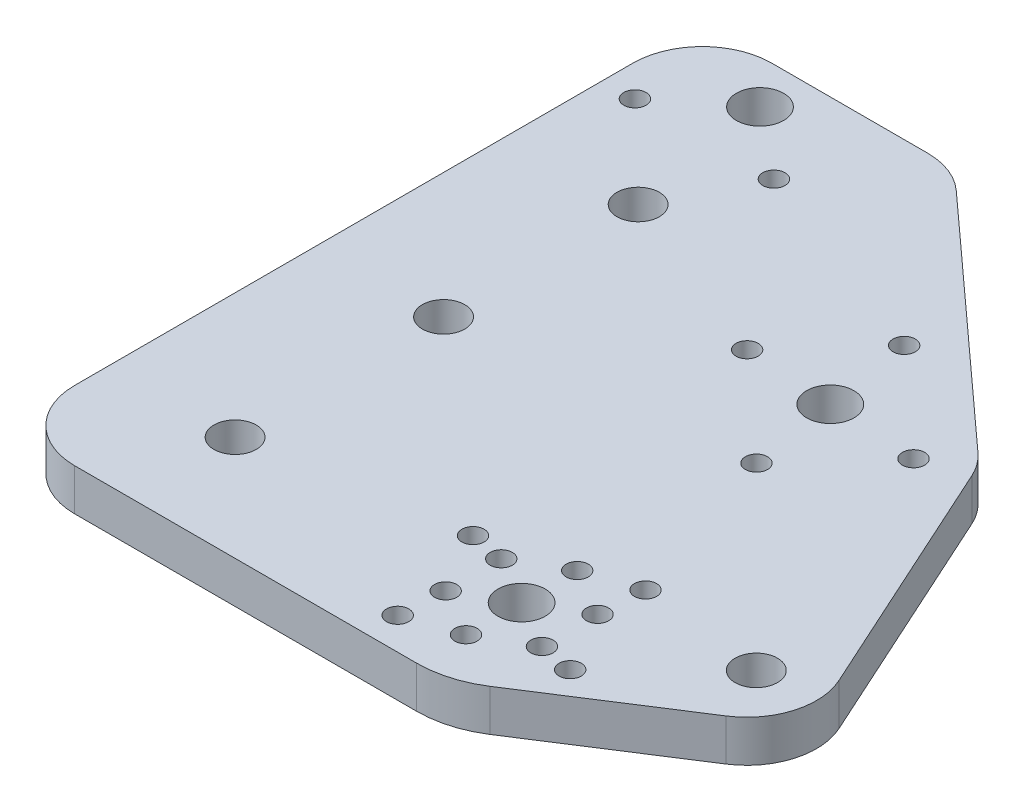
SolidWorks part; units mm, degrees
material "Policarbonato"
ref_plane "Plano frontal" through (0, 0, 0) normal (0, 0, 1) x (1, 0, 0)
ref_plane "Plano superior" through (0, 0, 0) normal (0, 1, 0) x (1, 0, 0)
ref_plane "Plano direito" through (0, 0, 0) normal (1, 0, 0) x (0, 0, -1)
ref_plane "Plano1" through (0, -6, 0) normal (0, -1, 0) x (1, 0, 0)
sketch "Esboço1" plane through (0, -6, 0) normal (0, -1, 0) x (1, 0, 0)
  line L0 (151.2357, -14.2909) -> (167.1948, 20.7865)
  line L1 (163.5005, 33.3393) -> (142.8288, 46.6294)
  line L2 (134.6661, 49.0269) -> (75.4374, 49.0269)
  line L3 (75.4374, 49.0269) -> (75.4374, -53)
  line L4 (78.4374, -56) -> (102.6847, -56)
  line L5 (109.4101, -53.4005) -> (148.859, -17.5502)
  line L6 (134.1775, -0.3541) -> (144.9383, -12.195) construction
  line L7 (144.9383, -12.195) -> (130.1372, -25.6459) construction
  line L8 (130.1372, -25.6459) -> (119.3765, -13.805) construction
  line L9 (119.3765, -13.805) -> (134.1775, -0.3541) construction
  line L10 (134.1775, -0.3541) -> (130.1372, -25.6459) construction
  line L11 (100.0374, -37) -> (80.0374, -53) construction
  line L12 (127.326, 44.4269) -> (146.5154, 38.7906) construction
  line L13 (146.5154, 38.7906) -> (142.0063, 23.4391) construction
  line L14 (142.0063, 23.4391) -> (122.8169, 29.0754) construction
  line L15 (122.8169, 29.0754) -> (127.326, 44.4269) construction
  line L16 (127.326, 44.4269) -> (142.0063, 23.4391) construction
  line L17 (134.6661, 33.933) -> (138.9199, 48.4151) construction
  line L18 (75.4374, -51.3) -> (111.7215, -51.3)
  circle A0 centre (119.3765, -13.805) radius 1.6
  circle A1 centre (146.5154, 38.7906) radius 1.6
  circle A2 centre (142.0063, 23.4391) radius 1.6
  circle A3 centre (159.9953, 25.4877) radius 3.05
  circle A4 centre (100.0374, -37) radius 1.6
  circle A5 centre (100.0374, -53) radius 1.6
  circle A6 centre (80.0374, -37) radius 1.6
  circle A7 centre (80.0374, -53) radius 1.6
  circle A8 centre (122.8169, 29.0754) radius 1.6
  circle A9 centre (127.326, 44.4269) radius 1.6
  circle A10 centre (130.1372, -25.6459) radius 1.6
  circle A11 centre (144.9383, -12.195) radius 1.6
  circle A12 centre (134.1775, -0.3541) radius 1.6
  circle A13 centre (141.5943, 29.933) radius 1.6
  circle A14 centre (134.6661, 25.933) radius 1.6
  circle A15 centre (127.7379, 29.933) radius 1.6
  circle A16 centre (127.7379, 37.933) radius 1.6
  circle A17 centre (134.6661, 41.933) radius 1.6
  circle A18 centre (141.5943, 37.933) radius 1.6
  circle A19 centre (134.6661, 33.933) radius 3.4
  circle A20 centre (132.1574, -13) radius 3.4
  circle A21 centre (90.0374, -45) radius 3.4
  arc A22 (167.1948, 20.7865) -> (163.5005, 33.3393) centre (158.0926, 24.9277) ccw
  arc A23 (142.8288, 46.6294) -> (134.6661, 49.0269) centre (134.6661, 33.933) ccw
  arc A24 (75.4374, -53) -> (78.4374, -56) centre (78.4374, -53) ccw
  arc A25 (102.6847, -56) -> (109.4101, -53.4005) centre (102.6847, -46) ccw
  arc A26 (148.859, -17.5502) -> (151.2357, -14.2909) centre (142.1335, -10.1497) ccw
  arc A27 (107.8564, -51.3) -> (114.5819, -48.7005) centre (107.8564, -41.3) ccw
  point P62 (134.6661, 33.933)
  dimension "D4" = 10
  dimension "D5" = 6.1
  dimension "D8" = 6.8
  dimension "D9" = 3.2
  dimension "D24" = 3
  dimension "D1" = 105.0269
  dimension "D2" = 11
  dimension "D3" = 82.6552
  dimension "D6" = 80.9277
  dimension "D7" = 137.736
  dimension "D10" = 20
  dimension "D11" = 16
  dimension "D12" = 6.6
  dimension "D13" = 52.897
  dimension "D14" = 43
  dimension "D15" = 16
  dimension "D16" = 90.676
  dimension "D17" = 59.2287
  dimension "D18" = 14.6
  dimension "D19" = 8
  dimension "D21" = 26.7
  dimension "D22" = 47.5
  dimension "D23" = 6.6
  dimension "D25" = 4.7
  dimension "D20" = 6
extrude "Ressalto-extrusão1" add sketch "Esboço1" against normal blind 6 contours L18 A27 L5 A26 L0 A22 L1 A23 L2 L3 A21 A19 A17 A15 A13 A11 A9 A3 A1 A0 A2 A4 A6 A8 A10 A12 A14 A16 A18 A20 region at (113.3527, -6, 3.5356)
sketch "Esboço2" plane through (0, -6, 0) normal (0, -1, 0) x (1, 0, 0)
  line L0 (75.4374, 49.0269) -> (75.4374, -51.3) construction
  line L1 (71.813, 11.433) -> (140.3089, 11.433) construction
  circle A0 centre (93.4374, 3.933) radius 3.05
  circle A1 centre (93.4374, -24.067) radius 3.05
  circle A2 centre (93.4374, 3.933) radius 7.5 construction
  circle A3 centre (93.4374, -24.067) radius 7.5 construction
  circle A4 centre (93.4374, 33.933) radius 3.05
  circle A5 centre (134.6661, 33.933) radius 3.4 construction
  dimension "D1" = 6.1
  dimension "D2" = 15
  dimension "D3" = 30
  dimension "D5" = 30
  dimension "D6" = 28
  dimension "D4" = 18
extrude "Corte-extrusão1" cut sketch "Esboço2" against normal blind 10 contours A1 | A0 | A4 region at (93.4374, -6, -24.067)
fillet "Filete1" radius 10 2 edges at (75.4374, -3, -51.3) (75.4374, -3, 49.0269)
